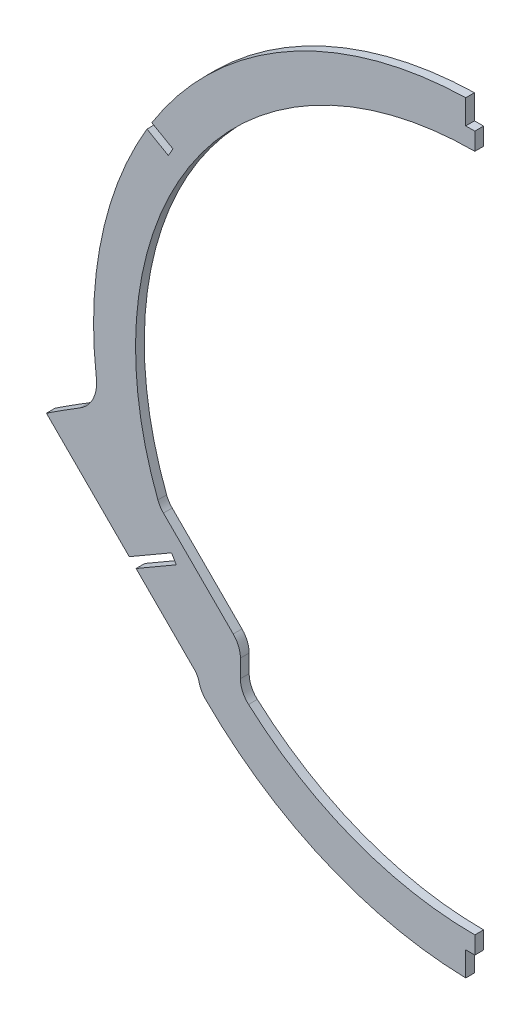
SolidWorks part; units mm, degrees
material "Balsa"
ref_plane "Front Plane" through (0, 0, 0) normal (0, 0, 1) x (1, 0, 0)
ref_plane "Top Plane" through (0, 0, 0) normal (0, 1, 0) x (1, 0, 0)
ref_plane "Right Plane" through (0, 0, 0) normal (1, 0, 0) x (0, 0, -1)
sketch "Sketch1" plane through (0, 0, 0) normal (0, 0, 1) x (1, 0, 0)
  line L0 (0, 32.094) -> (0, -346.2619) construction
  line L1 (0, 0) -> (0, 244.345) construction
  line L2 (0, 0) -> (0, 471.6969) construction
  line L3 (0, 0) -> (-283.5939, 0) construction
  line L4 (-127.2933, -32.5553) -> (-100.3525, -59.496)
  line L5 (-100.3525, -59.496) -> (-100.3525, -73.5092)
  line L6 (-100.3525, -59.496) -> (-54.3993, -105.4493) construction
  arc A0 (-54.3993, -105.4493) -> (-127.2933, -32.5553) centre (0, 21.844) ccw
  arc A2 (-100.3525, -73.5092) -> (-54.3993, -105.4493) centre (0, 21.844) ccw construction
  arc A3 (-127.2933, -32.5553) -> (-100.3525, -73.5092) centre (0, 21.844) ccw construction
  arc A4 (-100.3525, -73.5092) -> (-54.3993, -105.4493) centre (0, 21.844) ccw
  spline S2 degree 3 poles (-727.3087, -4752.7911) (287.5763, -944.0707) (320.9183, 35.1812) (49.9381, 150.9258) (45.7097, 152.4909) (37.1079, 155.2035) (32.7346, 156.3511) (27.1752, 157.5183) (26.0587, 157.7384) (23.8163, 158.1514) (22.6888, 158.3447) (19.306, 158.8811) (17.0511, 159.1813) (10.2867, 159.9126) (1.2693, 160.4377) (-7.745, 160.0789) (-14.5046, 159.4749) (-16.7575, 159.2176) (-20.1367, 158.7464) (-21.263, 158.5751) (-23.5156, 158.2037) (-24.6421, 158.0036) (-30.2426, 156.9366) (-34.6466, 155.8674) (-43.3063, 153.3113) (-47.562, 151.8242) (-55.9254, 148.4331) (-60.0331, 146.529) (-66.0807, 143.3516) (-68.0818, 142.2359) (-72.0044, 139.9197) (-73.9301, 138.7173) (-79.6017, 134.9792) (-86.884, 129.6473) (-93.6143, 123.6295) (-98.4521, 118.8554) (-100.0296, 117.2204) (-102.3424, 114.7015) (-103.1054, 113.8496) (-104.6077, 112.1297) (-105.3467, 111.2623) (-108.9818, 106.8875) (-111.6981, 103.2683) (-116.7574, 95.7975) (-119.1004, 91.9459) (-123.4121, 84.0098) (-125.3809, 79.9253) (-127.6006, 74.6695) (-128.0327, 73.61) (-128.8681, 71.4874) (-129.2719, 70.423) (-130.4422, 67.2205) (-131.1674, 65.0732) (-133.1812, 58.5951) (-135.4347, 49.861) (-136.834, 40.9354) (-137.5569, 34.168) (-137.7434, 31.9) (-137.9397, 28.4793) (-137.9911, 27.3374) (-138.0656, 25.0596) (-138.0887, 23.9223) (-138.135, 18.2442) (-137.9496, 13.7276) (-137.1441, 4.7454) (-136.5239, 0.2797) (-134.8456, -8.6005) (-133.7876, -13.015) (-131.2181, -21.791) (-129.7278, -26.0794) (-126.351, -34.4622) (-124.4643, -38.5569) (-120.2966, -46.5538) (-118.0156, -50.456) (-114.9122, -55.2108) (-114.2789, -56.1556) (-112.9868, -58.0327) (-112.3272, -58.9661) (-110.315, -61.7398) (-108.9333, -63.5482) (-104.6702, -68.8537) (-98.6716, -75.6089) (-92.0553, -81.7381) (-86.8592, -86.0978) (-85.0881, -87.5114) (-82.3719, -89.5716) (-81.4566, -90.2482) (-79.6058, -91.5811) (-78.6696, -92.238) (231.9603, -304.4561) (1345.3057, 781.0624) (3419.1463, 3416.8041) knots -1.975241 -1.975241 -1.975241 -1.975241 0.03125 0.03125 0.0625 0.0625 0.09375 0.09375 0.101563 0.101563 0.109375 0.109375 0.125 0.125 0.15625 0.1875 0.1875 0.203125 0.203125 0.210937 0.210937 0.21875 0.21875 0.25 0.25 0.28125 0.28125 0.3125 0.3125 0.328125 0.328125 0.34375 0.34375 0.375 0.40625 0.40625 0.421875 0.421875 0.429687 0.429687 0.4375 0.4375 0.46875 0.46875 0.5 0.5 0.53125 0.53125 0.539062 0.539062 0.546875 0.546875 0.5625 0.5625 0.59375 0.625 0.625 0.640625 0.640625 0.648437 0.648437 0.65625 0.65625 0.6875 0.6875 0.71875 0.71875 0.75 0.75 0.78125 0.78125 0.8125 0.8125 0.84375 0.84375 0.851562 0.851562 0.859375 0.859375 0.875 0.875 0.90625 0.9375 0.9375 0.953125 0.953125 0.960937 0.960937 0.96875 0.96875 3.533217 3.533217 3.533217 3.533217 only from (66.3397, 143.1887) to (-66.0465, -100.0388)
  spline S3 degree 3 poles (66.3397, 143.1887) (62.3323, 145.3909) (58.2494, 147.3758) (49.9381, 150.9258) (45.7097, 152.4909) (37.1079, 155.2035) (32.7346, 156.3511) (27.1752, 157.5183) (26.0587, 157.7384) (23.8163, 158.1514) (22.6888, 158.3447) (19.306, 158.8811) (17.0511, 159.1813) (10.2867, 159.9126) (1.2693, 160.4377) (-7.745, 160.0789) (-14.5046, 159.4749) (-16.7575, 159.2176) (-20.1367, 158.7464) (-21.263, 158.5751) (-23.5156, 158.2037) (-24.6421, 158.0036) (-30.2426, 156.9366) (-34.6466, 155.8674) (-43.3063, 153.3113) (-47.562, 151.8242) (-55.9254, 148.4331) (-60.0331, 146.529) (-66.0807, 143.3516) (-68.0818, 142.2359) (-72.0044, 139.9197) (-73.9301, 138.7173) (-79.6017, 134.9792) (-86.884, 129.6473) (-93.6143, 123.6295) (-98.4521, 118.8554) (-100.0296, 117.2204) (-102.3424, 114.7015) (-103.1054, 113.8496) (-104.6077, 112.1297) (-105.3467, 111.2623) (-108.9818, 106.8875) (-111.6981, 103.2683) (-116.7574, 95.7975) (-119.1004, 91.9459) (-123.4121, 84.0098) (-125.3809, 79.9253) (-127.6006, 74.6695) (-128.0327, 73.61) (-128.8681, 71.4874) (-129.2719, 70.423) (-130.4422, 67.2205) (-131.1674, 65.0732) (-133.1812, 58.5951) (-135.4347, 49.861) (-136.834, 40.9354) (-137.5569, 34.168) (-137.7434, 31.9) (-137.9397, 28.4793) (-137.9911, 27.3374) (-138.0656, 25.0596) (-138.0887, 23.9223) (-138.135, 18.2442) (-137.9496, 13.7276) (-137.1441, 4.7454) (-136.5239, 0.2797) (-134.8456, -8.6005) (-133.7876, -13.015) (-131.2181, -21.791) (-129.7278, -26.0794) (-127.6847, -31.1513) (-127.3213, -32.0275) (-126.9491, -32.8995) knots 0 0 0 0 0.03125 0.03125 0.0625 0.0625 0.09375 0.09375 0.101563 0.101563 0.109375 0.109375 0.125 0.125 0.15625 0.1875 0.1875 0.203125 0.203125 0.210937 0.210937 0.21875 0.21875 0.25 0.25 0.28125 0.28125 0.3125 0.3125 0.328125 0.328125 0.34375 0.34375 0.375 0.40625 0.40625 0.421875 0.421875 0.429687 0.429687 0.4375 0.4375 0.46875 0.46875 0.5 0.5 0.53125 0.53125 0.539062 0.539062 0.546875 0.546875 0.5625 0.5625 0.59375 0.625 0.625 0.640625 0.640625 0.648437 0.648437 0.65625 0.65625 0.6875 0.6875 0.71875 0.71875 0.75 0.75 0.78125 0.78125 0.787815 0.787815 0.787815 0.787815 construction
  point P2 (0, 160.2226)
  point P3 (0, -116.9127)
  point P23 (-100.3525, -59.496)
  dimension "D1" = 277.1353
  dimension "D2" = 276.86
  dimension "D3" = 21.844
  dimension "D5" = 45
  dimension "D6" = 113.03
  dimension "D4" = 38.1
  dimension "D7" = 45
extrude "Boss-Extrude1" add sketch "Sketch1" along normal mid plane 3.175
sketch "Sketch2" plane through (0, 0, 1.5875) normal (0, 0, 1) x (1, 0, 0)
  line L2 (-114.3729, -23.9231) -> (-85.1125, -53.1834)
  line L3 (-114.3729, -23.9231) -> (-85.1125, -53.1834)
  line L4 (-85.1125, -53.1834) -> (-85.1125, -67.2157)
  line L5 (-85.1125, -53.1834) -> (-85.1125, -67.2157)
  arc A2 (-85.1125, -67.2157) -> (-114.3729, -23.9231) centre (0, 21.844) ccw
  arc A3 (-85.1125, -67.2157) -> (-114.3729, -23.9231) centre (0, 21.844) ccw
  dimension "D1" = 15.24
extrude "Cut-Extrude1" cut sketch "Sketch2" against normal up to surface (3.175 mm away) up to face at (-32.8418, -4.8687, -1.5875)
fillet "Fillet1" radius 8.89 6 edges at (-127.2933, -32.5553, 0) (-114.3729, -23.9231, 0) (-100.3525, -59.496, 0) (-100.3525, -73.5092, 0) (-85.1125, -53.1834, 0) (-85.1125, -67.2157, 0)
sketch "Sketch3" plane through (0, 0, 1.5875) normal (0, 0, 1) x (1, 0, 0)
  line L0 (-0.0002, 49.9919) -> (-0.0176, 733.2) construction
  line L1 (-0.0002, 49.9919) -> (-0.0176, 733.2) construction
  line L2 (-136.2041, -28.3557) -> (-0.0002, 49.9919) construction
  line L3 (136.2076, -28.3488) -> (-0.0002, 49.9919) construction
  line L4 (-136.2041, -28.3557) -> (-0.0002, 49.9919) construction
  line L5 (136.2076, -28.3488) -> (-0.0002, 49.9919) construction
  line L6 (-1.6539, 152.6441) -> (-1.654, 160.2641)
  line L7 (1.6481, 152.6442) -> (1.648, 160.2642)
  line L8 (-1.6539, 152.6441) -> (1.6481, 152.6442)
  line L9 (119.8485, -45.962) -> (106.7537, -38.3747)
  line L10 (121.4435, -43.2066) -> (108.3479, -35.6188)
  line L18 (121.4435, -43.2066) -> (108.3479, -35.6188)
  line L30 (-123.167, -47.8929) -> (-104.8722, -37.2914)
  line L35 (119.8485, -45.962) -> (106.7537, -38.3747)
  line L47 (108.5244, -35.721) -> (120.1169, -46.1175) construction
  line L48 (114.3206, -40.9193) -> (126.5619, -48.0121) construction
  line L49 (113.8577, -42.5592) -> (122.0137, -47.2849)
  line L50 (115.5132, -39.7021) -> (123.6691, -44.4278)
  line L51 (113.8577, -42.5592) -> (115.5132, -39.7021)
  line L52 (122.0137, -47.2849) -> (123.6691, -44.4278)
  line L58 (-124.7703, -45.1423) -> (-106.4681, -34.5364)
  line L59 (-124.7703, -45.1423) -> (-123.167, -47.8929)
  line L71 (-124.7703, -45.1423) -> (-123.167, -47.8929) construction
  line L72 (-124.7703, -45.1423) -> (-106.4681, -34.5364) construction
  line L73 (-123.167, -47.8929) -> (-104.8722, -37.2914) construction
  line L74 (-123.167, -47.8929) -> (-107.9499, -35.3951) construction
  line L75 (-115.5584, -41.644) -> (-110.9064, -38.9482) construction
  line L76 (-119.3826, -41.9518) -> (-112.6266, -38.0369)
  line L77 (-117.727, -44.8088) -> (-110.971, -40.8938)
  line L78 (-119.3826, -41.9518) -> (-117.727, -44.8088)
  line L79 (-112.6266, -38.0369) -> (-110.971, -40.8938)
  arc A0 (-54.3993, -105.4493) -> (-127.2933, -32.5553) centre (0, 21.844) ccw construction
  arc A2 (-1.654, 160.2641) -> (-130.2816, -24.9489) centre (0, 21.844) ccw construction
  arc A3 (-130.2816, -24.9489) -> (-127.2933, -32.5553) centre (0, 21.844) ccw construction
  arc A4 (-1.654, 160.2641) -> (-130.2816, -24.9489) centre (0, 21.844) ccw construction
  arc A5 (-130.2816, -24.9489) -> (-127.9919, -30.8906) centre (0, 21.844) ccw construction
  arc A14 (130.2841, -24.9419) -> (1.648, 160.2642) centre (0, 21.844) ccw construction
  arc A15 (1.648, 160.2642) -> (-1.654, 160.2641) centre (0, 21.844) ccw
  arc A16 (130.2841, -24.9419) -> (1.648, 160.2642) centre (0, 21.844) ccw construction
  arc A17 (1.648, 160.2642) -> (-1.654, 160.2641) centre (0, 21.844) ccw
  spline S0 degree 3 poles (106.7537, -38.3747) (107.2851, -37.456) (107.8165, -36.5374) (108.3479, -35.6188) knots 0 0 0 0 1 1 1 1 weights 1 1 1 1
  spline S1 degree 3 poles (119.8485, -45.962) (120.3802, -45.0435) (120.9118, -44.1251) (121.4435, -43.2066) knots 0 0 0 0 1 1 1 1 weights 1 1 1 1
  spline S2 degree 3 poles (-3847.6145, -6688.6752) (-1193.4125, -2388.6207) (1509.1801, 2280.5122) (3904.1617, 6703.7111) knots -2509.987289 -2509.987289 -2509.987289 -2509.987289 2515.773198 2515.773198 2515.773198 2515.773198 weights 1.033987 0.988628 0.988671 1.034116 only from (119.8485, -45.962) to (121.4435, -43.2066)
  spline S3 degree 3 poles (-3959.2479, 6785.3642) (-1478.3785, 2275.755) (1214.3062, -2372.48) (3895.1026, -6773.1419) knots -2513.009721 -2513.009721 -2513.009721 -2513.009721 2512.935792 2512.935792 2512.935792 2512.935792 weights 1.021221 0.992932 0.992926 1.021203 only from (-106.4681, -34.5364) to (-104.8722, -37.2914)
  spline S4 degree 3 poles (-106.4681, -34.5364) (-105.9361, -35.4547) (-105.4042, -36.373) (-104.8722, -37.2914) knots 0 0 0 0 1 1 1 1 weights 1 1 1 1 construction
  spline S6 degree 3 poles (-3867.0162, -6706.7922) (-1202.4386, -2371.9097) (1495.677, 2292.8781) (3905.6981, 6731.4638) knots -2508.399086 -2508.399086 -2508.399086 -2508.399086 2517.428296 2517.428296 2517.428296 2517.428296 weights 1.03062 0.989729 0.989792 1.030818 only from (106.7537, -38.3747) to (108.3479, -35.6188)
  point P49 (-116.0256, -43.8229)
  point P50 (120.451, -46.3794)
  dimension "D1" = 3.302
  dimension "D2" = 7.62
  dimension "D4" = 3.302
  dimension "D5" = 7.62
  dimension "D6" = 3.302
  dimension "D7" = 5.842
sketch "Sketch4" plane through (0, 0, 0) normal (1, 0, 0) x (0, 0, -1)
  line L1 (-96.2805, 232.7957) -> (122.2438, 232.7957)
  line L2 (-96.2805, 232.7957) -> (-96.2805, -207.8589)
  line L3 (-96.2805, -207.8589) -> (122.2438, -207.8589)
  line L4 (122.2438, 232.7957) -> (122.2438, -207.8589)
extrude "Cut-Extrude3" cut sketch "Sketch4" along normal through all
sketch "Sketch5" plane through (0, 0, 0) normal (0, 0, 1) x (1, 0, 0)
  line L0 (0, 0) -> (-220.3195, 0) construction
  line L3 (-100.3441, -70.2779) -> (-93.132, -63.0671)
  line L4 (-100.3441, -70.2779) -> (-155.5427, -15.0686)
  line L5 (-93.132, -63.0671) -> (-135.3862, -2.54)
  arc A0 (-100.3525, -69.8905) -> (-97.7394, -76.186) centre (-91.4625, -69.8905) ccw construction
  arc A1 (-135.3862, -2.54) -> (-155.5427, -15.0686) centre (85.5484, -380.4649) ccw
  dimension "D3" = 437.7663
  dimension "D1" = 120.65
  dimension "D2" = 45.006
  dimension "D4" = 135.3862
  dimension "D5" = 2.54
  dimension "D6" = 15.0686
extrude "Boss-Extrude2" add sketch "Sketch5" along normal mid plane 3.175
fillet "Fillet2" radius 12.7 1 edges at (-136.1813, -3.0059, 0)
fillet "Fillet3" radius 6.35 1 edges at (-100.3441, -70.2779, 0)
sketch "Sketch6" plane through (0, 0, -1.5875) normal (0, 0, -1) x (-1, 0, 0)
  line L0 (0, 0) -> (0, 145.034) construction
  line L1 (0, 145.034) -> (0, 151.384) construction
  line L2 (0, 145.034) -> (0, 160.274) construction
  line L3 (104.929, 86.3862) -> (0, 26.2525) construction
  line L4 (0, 151.384) -> (3.302, 151.384)
  line L5 (0, 151.384) -> (0, 164.084)
  line L6 (0, 164.084) -> (3.302, 164.084)
  line L7 (3.302, 151.384) -> (3.302, 164.084)
  line L14 (104.929, 86.3862) -> (110.4384, 89.5435) construction
  line L15 (109.5985, 91.009) -> (111.2782, 88.078)
  line L16 (109.5985, 91.009) -> (120.6173, 97.3238)
  line L17 (111.2782, 88.078) -> (122.297, 94.3928)
  line L18 (120.6173, 97.3238) -> (122.297, 94.3928)
  line L26 (103.7614, -34.5345) -> (0, 25.5937) construction
  line L27 (103.7614, -34.5345) -> (109.2556, -37.7183) construction
  line L28 (108.4087, -39.1798) -> (110.1025, -36.2569)
  line L29 (108.4087, -39.1798) -> (124.8912, -48.7311)
  line L30 (110.1025, -36.2569) -> (126.585, -45.8082)
  line L31 (124.8912, -48.7311) -> (126.585, -45.8082)
  line L32 (0, 0) -> (0, -101.346) construction
  line L33 (0, -101.346) -> (0, -107.696) construction
  line L36 (0, -107.696) -> (3.302, -107.696)
  line L37 (0, -107.696) -> (0, -120.396)
  line L38 (0, -120.396) -> (3.302, -120.396)
  line L39 (3.302, -107.696) -> (3.302, -120.396)
  point P3 (110.4384, 89.5435)
  point P15 (109.2556, -37.7183)
  dimension "D13" = 6.35
  dimension "D1" = 151.384
  dimension "D2" = 12.7
  dimension "D3" = 3.302
  dimension "D4" = 60.183
  dimension "D5" = 26.2525
  dimension "D6" = 120.9386
  dimension "D7" = 6.35
  dimension "D8" = 3.3782
  dimension "D9" = 12.7
  dimension "D10" = 59.908
  dimension "D11" = 25.5937
  dimension "D12" = 119.9243
  dimension "D14" = 3.3782
  dimension "D15" = 19.05
  dimension "D16" = 6.35
  dimension "D17" = 107.696
  dimension "D18" = 12.7
  dimension "D19" = 3.302
extrude "Cut-Extrude4" cut sketch "Sketch6" against normal through all
equation "\"a\"= 0.06"
equation "\"slotwidth\"=0.13"
equation "\"slotheight\"=0.3"
